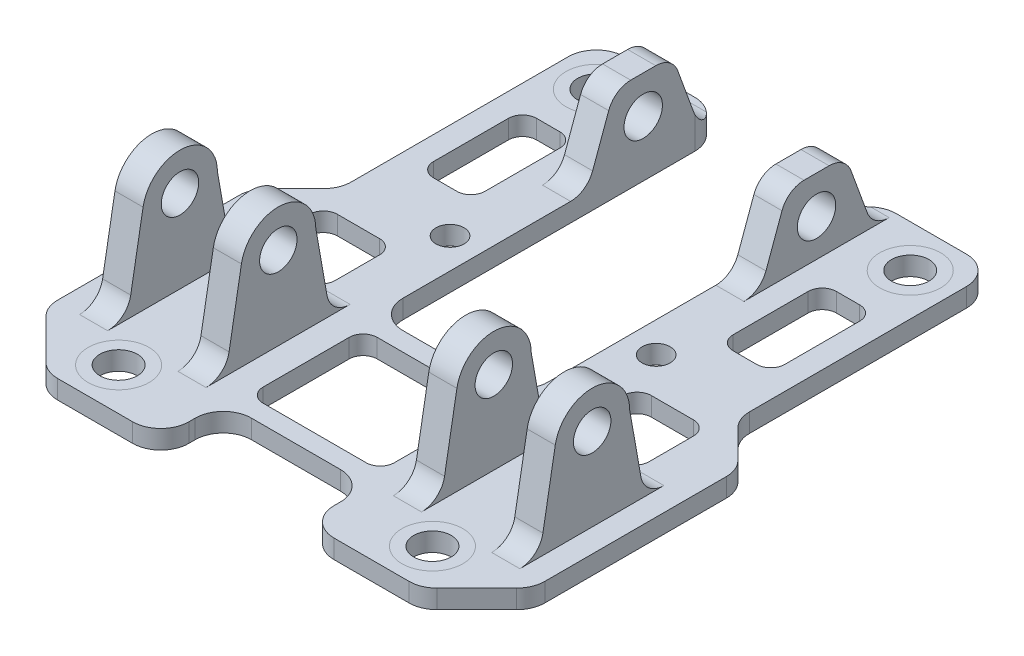
SolidWorks part; units mm, degrees
material "6061-T6 (SS)"
ref_plane "Front Plane" through (0, 0, 0) normal (0, 0, 1) x (1, 0, 0)
ref_plane "Top Plane" through (0, 0, 0) normal (0, 1, 0) x (1, 0, 0)
ref_plane "Right Plane" through (0, 0, 0) normal (1, 0, 0) x (0, 0, -1)
sketch "Sketch1" plane through (0, 0, 0) normal (1, 0, 0) x (0, 0, -1)
  line L0 (14.6775, -14.524) -> (20.501, 1.476)
  line L1 (20.501, 1.476) -> (32.854, 1.476)
  line L3 (14.6775, -14.524) -> (38.6775, -14.524)
  line L5 (19.3639, -1.6483) -> (38.6775, -14.524) construction
  line L6 (14.6775, -14.524) -> (33.9911, -1.6483) construction
  line L7 (38.6775, -14.524) -> (32.854, 1.476)
  line L8 (-54.6019, 4.5505) -> (-57.9653, -14.524)
  line L9 (43.6775, -14.524) -> (-76.3225, -14.524)
  line L10 (43.6775, -14.524) -> (43.6775, -18.524)
  line L11 (43.6775, -18.524) -> (-76.3225, -18.524)
  line L12 (-76.3225, -14.524) -> (-76.3225, -18.524)
  line L13 (-57.9653, -14.524) -> (-35.605, -14.524)
  line L14 (-35.605, -14.524) -> (-38.7234, 3.1613)
  circle A0 centre (26.6775, -6.524) radius 4.1
  circle A1 centre (-46.7234, 3.1613) radius 4
  arc A2 (-38.7234, 3.1613) -> (-54.6019, 4.5505) centre (-46.7234, 3.1613) ccw
  dimension "D1" = 8
  dimension "D2" = 8.2
  dimension "D10" = 16
  dimension "D3" = 24
  dimension "D4" = 16
  dimension "D5" = 70
  dimension "D6" = 70
  dimension "D7" = 4
  dimension "D8" = 120
  dimension "D9" = 5
  dimension "D11" = 80
  dimension "D12" = 80
extrude "Boss-Extrude1" add sketch "Sketch1" along normal blind 52 and the other way blind 52 contours L9 L12 L11 L10
extrude "Boss-Extrude2" add sketch "Sketch1<3>" against normal blind 6 from offset 20 contours L14 A2 L8 L13 | A1 offset against normal yes
sketch "Sketch1<3>" plane through (0, 0, 0) normal (1, 0, 0) x (0, 0, -1) same geometry as "Sketch1"
pattern_linear "LPattern1" count 2 spacing 21 along (1, 0, 0) of "Boss-Extrude2"
extrude "Boss-Extrude3" add sketch "Sketch1<4>" against normal blind 6 from offset 15.5 contours L1 L7 L3 L0 | A0 offset against normal yes
sketch "Sketch1<4>" plane through (0, 0, 0) normal (1, 0, 0) x (0, 0, -1) same geometry as "Sketch1"
sketch "Sketch2" plane through (0, -14.524, 0) normal (0, 1, 0) x (1, 0, 0)
  line L0 (-41, -35.605) -> (-26, -35.605) construction
  line L1 (-33.5, -76.3225) -> (-33.5, 43.6775) construction
  line L2 (-52, -76.3225) -> (52, -76.3225) construction
  line L3 (-52, 43.6775) -> (52, 43.6775) construction
  line L5 (-52, -76.3225) -> (-40, -76.3225)
  line L6 (-40, -76.3225) -> (-52, -64.3225)
  line L7 (-52, 43.6775) -> (-52, -76.3225) construction
  line L8 (-52, -64.3225) -> (-52, -76.3225)
  line L9 (-42.5, 43.6775) -> (-42.5, -11.105)
  line L11 (-52, -20.605) -> (-52, 43.6775)
  line L12 (-52, 43.6775) -> (-42.5, 43.6775)
  line L14 (-52, -20.605) -> (-42.5, -11.105)
  line L15 (-47, -35.605) -> (-41, -35.605) construction
  line L16 (-26, -35.605) -> (-20, -35.605) construction
  line L17 (0, 43.6775) -> (-15.5, 43.6775)
  line L18 (0, 43.6775) -> (0, -30.605)
  line L19 (0, -30.605) -> (-15.5, -30.605)
  line L20 (-15.5, 43.6775) -> (-15.5, -30.605)
  line L21 (0, 43.6775) -> (0, -76.3225) construction
  line L22 (-15.5, -76.3225) -> (0, -76.3225)
  line L23 (-15.5, -76.3225) -> (-15.5, -62.9653)
  line L24 (-15.5, -62.9653) -> (0, -62.9653)
  line L25 (0, -76.3225) -> (0, -62.9653)
  line L26 (-26, -57.9653) -> (-20, -57.9653) construction
  circle A0 centre (-33.5, -67.3225) radius 4
  circle A1 centre (-33.5, 34.6775) radius 4
  point P26 (-33.5, -35.605)
  dimension "D1" = 8
  dimension "D2" = 8
  dimension "D3" = 9
  dimension "D4" = 9
  dimension "D5" = 45
  dimension "D6" = 12
  dimension "D7" = 9
  dimension "D8" = 15
  dimension "D9" = 45
  dimension "D10" = 5
  dimension "D11" = 5
extrude "Cut-Extrude1" cut sketch "Sketch2" against normal through all
mirror "Mirror2" about plane through (0, 0, 0) normal (1, 0, 0) of "Boss-Extrude3", "LPattern1", "Boss-Extrude2", "Cut-Extrude1"
sketch "Sketch3" plane through (0, -14.524, 0) normal (0, 1, 0) x (1, 0, 0)
  circle A0 centre (-33.5, 34.6775) radius 6.5
  circle A1 centre (33.5, 34.6775) radius 6.5
  circle A2 centre (-33.5, -67.3225) radius 6.5
  circle A3 centre (33.5, -67.3225) radius 6.5
  dimension "D1" = 13
  dimension "D2" = 13
  dimension "D3" = 13
  dimension "D4" = 13
split line "Split Line1"
sketch "Sketch4" plane through (0, -14.524, 0) normal (0, 1, 0) x (1, 0, 0)
  circle A0 centre (22, -8.0646) radius 3
  circle A1 centre (-22, -8.0646) radius 3
extrude "Cut-Extrude2" cut sketch "Sketch4" against normal blind 10
sketch "Sketch5" plane through (0, -14.524, 0) normal (0, 1, 0) x (1, 0, 0)
  line L0 (-42.5, -11.105) -> (-42.5, 43.6775) construction
  line L1 (-41, -31.605) -> (-26, -31.605)
  line L2 (-41, -31.605) -> (-41, -16.105)
  line L3 (-41, -16.105) -> (-26, -16.105)
  line L4 (-26, -31.605) -> (-26, -16.105)
  line L5 (-26.5, 0.895) -> (-37.5, 0.895)
  line L6 (-26.5, 0.895) -> (-26.5, 22.895)
  line L7 (-26.5, 22.895) -> (-37.5, 22.895)
  line L8 (-37.5, 0.895) -> (-37.5, 22.895)
  line L9 (-21.5, 14.6775) -> (-21.5, 38.6775) construction
  line L11 (14, -34.605) -> (-14, -34.605)
  line L13 (14, -58.9653) -> (-14, -58.9653)
  line L14 (-14, -34.605) -> (-14, -58.9653)
  line L15 (-15.5, -30.605) -> (15.5, -30.605) construction
  line L16 (15.5, -62.9653) -> (-15.5, -62.9653) construction
  line L17 (-20, -57.9653) -> (-20, -35.605) construction
  line L18 (0, -16.3269) -> (0, 16.3269) construction
  line L19 (14, -34.605) -> (14, -58.9653)
  line L20 (41, -16.105) -> (26, -16.105)
  line L21 (26, -31.605) -> (26, -16.105)
  line L22 (41, -31.605) -> (26, -31.605)
  line L23 (41, -31.605) -> (41, -16.105)
  line L24 (26.5, 22.895) -> (37.5, 22.895)
  line L25 (37.5, 0.895) -> (37.5, 22.895)
  line L26 (26.5, 0.895) -> (37.5, 0.895)
  line L27 (26.5, 0.895) -> (26.5, 22.895)
  dimension "D1" = 4
  dimension "D2" = 5
  dimension "D3" = 5
  dimension "D4" = 5
  dimension "D5" = 17
  dimension "D6" = 22
  dimension "D7" = 4
  dimension "D8" = 4
  dimension "D9" = 6
extrude "Cut-Extrude3" cut sketch "Sketch5" against normal blind 10 contours L8 L5 L6 L7 | L1 L4 L3 L2 | L11 L14 L13 | L19 L11 L13 | L22 L23 L20 L21 | L27 L26 L25 L24 region at (-33.5, -14.524, 23.855) region at (-32, -14.524, -11.895) region at (0, -14.524, 46.7852) region at (33.5, -14.524, 23.855) region at (32, -14.524, -11.895)
fillet "Fillet1" radius 6 18 edges at (40, -16.524, 76.3225) (52, -16.524, 64.3225) (52, -16.524, 20.605) (42.5, -16.524, 11.105) (42.5, -16.524, -43.6775) (15.5, -16.524, -43.6775) (-15.5, -16.524, -43.6775) (-42.5, -16.524, -43.6775) (-42.5, -16.524, 11.105) (-52, -16.524, 20.605) (-52, -16.524, 64.3225) (-40, -16.524, 76.3225) (15.5, -16.524, 76.3225) (-15.5, -16.524, 76.3225) (15.5, -16.524, 62.9653) (-15.5, -16.524, 62.9653) (-15.5, -16.524, 30.605) (15.5, -16.524, 30.605)
fillet "Fillet2" radius 3 20 edges at (-37.5, -16.524, -22.895) (-26.5, -16.524, -22.895) (-26.5, -16.524, -0.895) (-37.5, -16.524, -0.895) (-41, -16.524, 31.605) (-26, -16.524, 31.605) (-41, -16.524, 16.105) (-26, -16.524, 16.105) (37.5, -16.524, -22.895) (26.5, -16.524, -22.895) (37.5, -16.524, -0.895) (26.5, -16.524, -0.895) (41, -16.524, 16.105) (26, -16.524, 16.105) (26, -16.524, 31.605) (41, -16.524, 31.605) (14, -16.524, 58.9653) (14, -16.524, 34.605) (-14, -16.524, 34.605) (-14, -16.524, 58.9653)
fillet "Fillet3" radius 5 16 edges at (-44, -14.524, 57.9653) (-23, -14.524, 57.9653) (23, -14.524, 57.9653) (44, -14.524, 57.9653) (-44, -14.524, 35.605) (-23, -14.524, 35.605) (23, -14.524, 35.605) (44, -14.524, 35.605) (-18.5, 1.476, -20.501) (-18.5, -14.524, -14.6775) (-18.5, 1.476, -32.854) (-18.542, -14.524, -38.6775) (18.542, -14.524, -38.6775) (18.5, 1.476, -32.854) (18.5, 1.476, -20.501) (18.5, -14.524, -14.6775)
